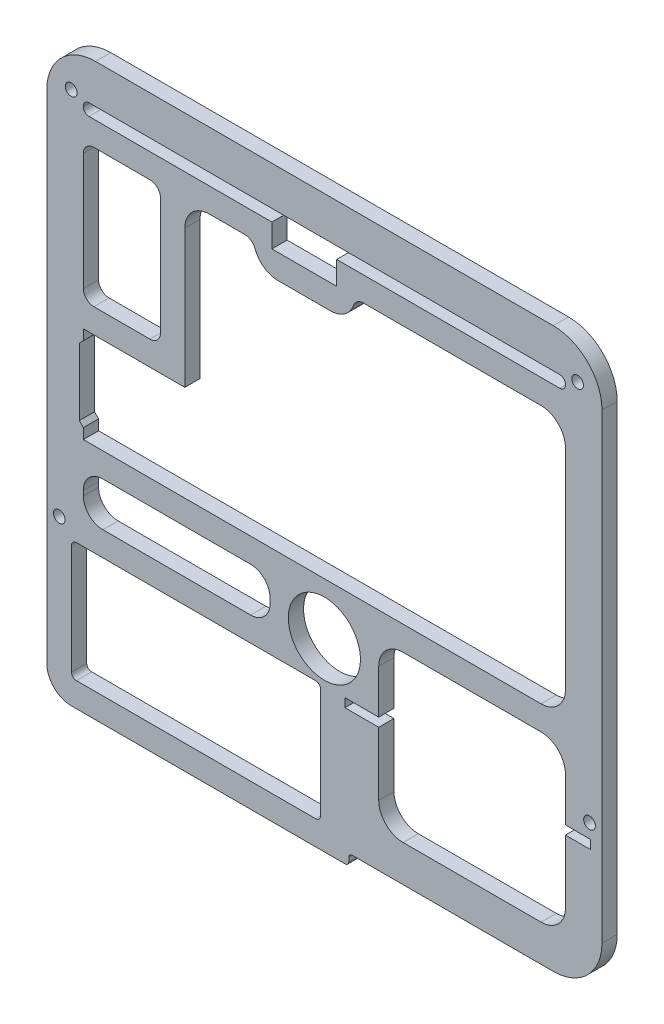
SolidWorks part; units mm, degrees
ref_plane "Front Plane" through (0, 0, 0) normal (0, 0, 1) x (1, 0, 0)
ref_plane "Top Plane" through (0, 0, 0) normal (0, 1, 0) x (1, 0, 0)
ref_plane "Right Plane" through (0, 0, 0) normal (1, 0, 0) x (0, 0, -1)
sketch "Sketch1" plane through (0, 0, 0) normal (0, 0, 1) x (1, 0, 0)
  line L0 (63.9883, 50.6392) -> (63.9883, 46.8292) construction
  line L1 (6.1648, -7.651) -> (64.0322, -7.651)
  line L2 (6.1648, -7.651) -> (6.1648, 50.6392)
  line L3 (6.1648, 50.6392) -> (64.0322, 50.6392)
  line L4 (64.0322, -7.651) -> (64.0322, 50.6392)
  line L5 (60.2222, 46.8292) -> (9.9748, 46.8292)
  line L6 (60.2222, 46.8292) -> (60.2222, -3.841)
  line L7 (60.2222, -3.841) -> (9.9748, -3.841)
  line L8 (9.9748, 46.8292) -> (9.9748, -3.841)
  line L9 (63.9883, 48.7342) -> (18.0707, 48.7342) construction
  line L10 (9.9748, 41.2855) -> (6.1648, 41.2855) construction
  line L11 (8.0698, 41.2855) -> (8.0698, 25.8577) construction
  line L12 (13.5248, -3.841) -> (13.5248, -7.651) construction
  line L13 (13.5248, -5.746) -> (21.1598, -5.746) construction
  line L14 (64.0322, 38.1916) -> (60.2222, 38.1916) construction
  line L15 (62.1272, 38.1916) -> (62.1272, 22.3321) construction
  line L22 (34.9556, 48.7342) -> (35.5018, 48.7342) construction
  line L23 (52.4244, -5.746) -> (51.8782, -5.746) construction
  line L24 (8.0698, 15.868) -> (8.0698, 3.6252) construction
  line L25 (62.1272, 27.1202) -> (62.1272, 39.363) construction
  dimension "D1" = 3.81
  dimension "D2" = 3.81
extrude "Boss-Extrude1" add sketch "Sketch1" along normal blind 1.5875
sketch "Sketch2" plane through (0, 0, 0) normal (0, 0, -1) x (-1, 0, 0)
  line L0 (-60.2222, -3.841) -> (-60.2222, 46.8292) construction
  line L1 (-60.2222, 15.868) -> (-9.9748, 15.868)
  line L2 (-60.2222, 15.868) -> (-60.2222, 13.328)
  line L3 (-60.2222, 13.328) -> (-9.9748, 13.328)
  line L4 (-9.9748, 15.868) -> (-9.9748, 13.328)
  line L5 (-9.9748, 46.8292) -> (-9.9748, -3.841) construction
  line L11 (-60.2222, 45.3306) -> (-36.3812, 45.3306)
  line L12 (-60.2222, 45.3306) -> (-60.2222, 42.7906)
  line L13 (-60.2222, 42.7906) -> (-38.2862, 42.7906)
  line L14 (-9.9748, 45.3306) -> (-9.9748, 42.7906)
  line L15 (-60.2222, 47.8325) -> (-9.9748, 47.8325)
  line L16 (-60.2222, 47.8325) -> (-60.2222, 46.5625)
  line L17 (-60.2222, 46.5625) -> (-9.9748, 46.5625)
  line L18 (-9.9748, 47.8325) -> (-9.9748, 46.5625)
  line L22 (-36.3812, 42.9049) -> (-36.3812, 45.3306)
  line L23 (-29.6248, 42.9049) -> (-36.3812, 42.9049)
  line L24 (-29.6248, 42.9049) -> (-29.6248, 45.3306)
  line L25 (-38.2862, 42.7906) -> (-38.2862, 40.3649)
  line L26 (-38.2862, 40.3649) -> (-27.7198, 40.3649)
  line L27 (-27.7198, 40.3649) -> (-27.7198, 42.7906)
  line L28 (-27.7198, 42.7906) -> (-9.9748, 42.7906)
  line L29 (-29.6248, 45.3306) -> (-9.9748, 45.3306)
  dimension "D1" = 2.54
  dimension "D2" = 1.905
  dimension "D3" = 2.54
  dimension "D4" = 1.905
  dimension "D5" = 1.27
extrude "Boss-Extrude2" add sketch "Sketch2" against normal up to surface (1.5875 mm away) up to face at (35.0985, 21.4941, 1.5875)
sketch "Sketch3" plane through (0, 0, 0) normal (0, 0, -1) x (-1, 0, 0)
  line L1 (-16.3032, 25.868) -> (-9.9748, 25.868) construction
  line L12 (-20.5532, 25.868) -> (-13.0532, 25.868)
  line L13 (-13.0532, 25.868) -> (-9.9748, 25.868)
  line L14 (-9.9748, 42.7906) -> (-9.9748, 15.868) construction
  line L15 (-9.9748, 25.868) -> (-9.9748, 28.408)
  line L16 (-9.9748, 28.408) -> (-18.0132, 28.408)
  line L17 (-18.0132, 28.408) -> (-18.0132, 42.7906)
  line L18 (-27.7198, 42.7906) -> (-9.9748, 42.7906) construction
  line L19 (-18.0132, 42.7906) -> (-20.5532, 42.7906)
  line L20 (-20.5532, 42.7906) -> (-20.5532, 25.868)
  line M27 (-27.7198, 42.7906) -> (-9.9748, 42.7906)
  line M28 (-9.9748, 42.7906) -> (-9.9748, 15.868)
  dimension "D3" = 2.54
  dimension "D4" = 2.54
extrude "Boss-Extrude3" add sketch "Sketch3" against normal up to surface (1.5875 mm away) contours L20 L12 L13 L16 L17 M27 M28 region at (20.3536, 34.3293, 0) up to face at (34.0507, 45.0322, 1.5875)
sketch "Sketch4" plane through (0, 0, 0) normal (0, 0, -1) x (-1, 0, 0)
  line L0 (-60.2222, 13.328) -> (-9.9748, 13.328) construction
  line L1 (-40.7627, 13.328) -> (-29.4343, 13.328)
  line L2 (-40.7627, 13.328) -> (-40.7627, -3.841)
  line L3 (-40.7627, -3.841) -> (-29.4343, -3.841)
  line L4 (-29.4343, 13.328) -> (-29.4343, -3.841)
  line L5 (-9.9748, -3.841) -> (-60.2222, -3.841) construction
  line L6 (-38.8577, 10.4578) -> (-40.7627, 10.4578) construction
  line L7 (-31.3393, 10.4578) -> (-29.4343, 10.4578) construction
  dimension "D1" = 1.905
extrude "Boss-Extrude4" add sketch "Sketch4" against normal up to surface (1.5875 mm away) up to face at (13.994, 35.5993, 1.5875)
sketch "Sketch5" plane through (0, 0, 0) normal (0, 0, -1) x (-1, 0, 0)
  line L1 (-8.7364, -6.254) -> (-34.6952, -6.254) construction
  line L2 (-8.7364, -6.254) -> (-8.7364, 6.2047) construction
  line L6 (-8.7364, 6.2047) -> (-34.6952, 6.2047) construction
  line L7 (-34.6952, -6.254) -> (-34.6952, 6.2047) construction
  line L8 (-8.7364, -6.254) -> (-34.6952, -6.254)
  line L9 (-8.7364, -6.254) -> (-8.7364, 6.2047)
  line L10 (-8.7364, 6.2047) -> (-34.6952, 6.2047)
  line L11 (-34.6952, -6.254) -> (-34.6952, 6.2047)
  circle A1 centre (-35.0985, 10.4578) radius 3.7592 construction
  circle A2 centre (-35.0985, 10.4578) radius 3.7592
extrude "Cut-Extrude1" cut sketch "Sketch5" against normal up to surface (1.5875 mm away) up to face at (50.4924, 4.7435, 1.5875)
sketch "Sketch10" plane through (0, 0, 1.5875) normal (0, 0, 1) x (1, 0, 0)
  line L0 (29.4343, 13.328) -> (29.4343, 6.2047) construction
  line L1 (9.9748, 6.2047) -> (29.4343, 6.2047)
  line L2 (9.9748, 6.2047) -> (9.9748, 8.7447)
  line L3 (9.9748, 8.7447) -> (29.4343, 8.7447)
  line L4 (29.4343, 6.2047) -> (29.4343, 8.7447)
  dimension "D1" = 2.54
extrude "Boss-Extrude5" add sketch "Sketch10" against normal up to surface (1.5875 mm away) up to face at (20.7101, 4.8709, 0)
fillet "Fillet1" radius 5.08 3 edges at (64.0322, -7.651, 0.7937) (6.1648, 50.6392, 0.7937) (64.0322, 50.6392, 0.7937)
fillet "Fillet2" radius 2.54 5 edges at (20.5532, 42.7906, 0.7937) (27.7198, 40.3649, 0.7937) (60.2222, 42.7906, 0.7937) (60.2222, 15.868, 0.7937) (38.2862, 40.3649, 0.7937)
fillet "Fillet3" radius 1.0922 6 edges at (9.9748, 28.408, 0.7937) (18.0132, 28.408, 0.7937) (9.9748, 42.7906, 0.7937) (18.0132, 42.7906, 0.7937) (27.7198, 42.7906, 0.7937) (38.2862, 42.7906, 0.7937)
fillet "Fillet4" radius 0.5842 4 edges at (9.9748, 45.3306, 0.7937) (9.9748, 46.5625, 0.7937) (60.2222, 46.5625, 0.7937) (60.2222, 45.3306, 0.7937)
sketch "Sketch6" plane through (0, 0, 0) normal (0, 0, -1) x (-1, 0, 0)
  line L0 (-9.5532, 24.368) -> (-9.5532, 17.368) construction
  line L1 (-9.5532, 24.368) -> (-9.5532, 17.368)
  line L2 (-11.0532, 25.868) -> (-9.5532, 24.368) construction
  line L3 (-11.0532, 25.868) -> (-9.5532, 24.368)
  line L4 (-11.0532, 25.868) -> (-11.0532, 15.868)
  line L6 (-13.0532, 17.368) -> (-13.0532, 15.868)
  line L7 (-13.0532, 15.868) -> (-11.0532, 15.868)
  line L8 (-11.0532, 15.868) -> (-9.5532, 17.368)
  line L9 (-9.5532, 17.368) -> (-13.0532, 17.368)
  line L12 (-11.0532, 15.868) -> (-9.5532, 17.368)
  circle A0 centre (-61.4922, 46.8292) radius 0.6096 construction
  circle A1 centre (-8.7048, 46.8292) radius 0.6096 construction
  circle A2 centre (-62.7368, 7.6638) radius 0.6096 construction
  circle A3 centre (-7.4602, 7.6638) radius 0.6096 construction
  circle A4 centre (-61.4922, 46.8292) radius 0.6096
  circle A5 centre (-8.7048, 46.8292) radius 0.6096
  circle A6 centre (-62.7368, 7.6638) radius 0.6096
  circle A7 centre (-7.4602, 7.6638) radius 0.6096
  dimension "D1" = 0
extrude "Cut-Extrude2" cut sketch "Sketch6" against normal up to surface (1.5875 mm away) up to face at (21.7158, -0.0246, 1.5875)
sketch "Sketch9" plane through (0, 0, 1.5875) normal (0, 0, 1) x (1, 0, 0)
  line L4 (62.813, 6.2047) -> (37.2352, 6.2047)
  line L5 (37.2352, 6.2047) -> (37.2352, 5.2903)
  line L6 (37.2352, 5.2903) -> (62.813, 5.2903)
  line L7 (62.813, 5.2903) -> (62.813, 6.2047)
  line L8 (62.813, 6.2047) -> (37.2352, 6.2047)
  line L9 (37.2352, 6.2047) -> (37.2352, 5.2903)
  line L10 (37.2352, 5.2903) -> (62.813, 5.2903)
  line L11 (62.813, 5.2903) -> (62.813, 6.2047)
  dimension "D1" = 0
extrude "Cut-Extrude3" cut sketch "Sketch9" against normal up to surface (1.5875 mm away) up to face at (29.3451, 31.6821, 0)
fillet "Fillet6" radius 0.508 4 edges at (34.6952, 6.2047, 0.7937) (34.6952, -6.254, 0.7937) (8.7364, 6.2047, 0.7937) (8.7364, -6.254, 0.7937)
sketch "Sketch11" plane through (0, 0, 1.5875) normal (0, 0, 1) x (1, 0, 0)
  line L0 (9.2444, -6.254) -> (34.1872, -6.254) construction
  line L1 (6.1648, -7.651) -> (37.6385, -7.651)
  line L2 (6.1648, -7.651) -> (6.1648, -8.794)
  line L3 (6.1648, -8.794) -> (37.6385, -8.794)
  line L4 (37.6385, -7.651) -> (37.6385, -8.794)
  line L5 (35.0985, 14.217) -> (35.0985, -22.2214) construction
  circle A0 centre (35.0985, 10.4578) radius 3.7592 construction
  dimension "D1" = 2.54
  dimension "D2" = 2.54
extrude "Boss-Extrude6" add sketch "Sketch11" against normal up to surface (1.5875 mm away) up to face at (50.3363, 5.4129, 0)
fillet "Fillet7" radius 2.54 1 edges at (6.1648, -8.794, 0.7937)
fillet "Fillet8" radius 0.381 2 edges at (37.6385, -8.794, 0.7937) (37.6385, -7.651, 0.7937)
fillet "Fillet9" radius 2.032 4 edges at (29.4343, 8.7447, 0.7937) (29.4343, 13.328, 0.7937) (9.9748, 8.7447, 0.7937) (9.9748, 13.328, 0.7937)
fillet "Fillet10" radius 2.54 4 edges at (40.7627, -3.841, 0.7937) (60.2222, -3.841, 0.7937) (60.2222, 13.328, 0.7937) (40.7627, 13.328, 0.7937)
